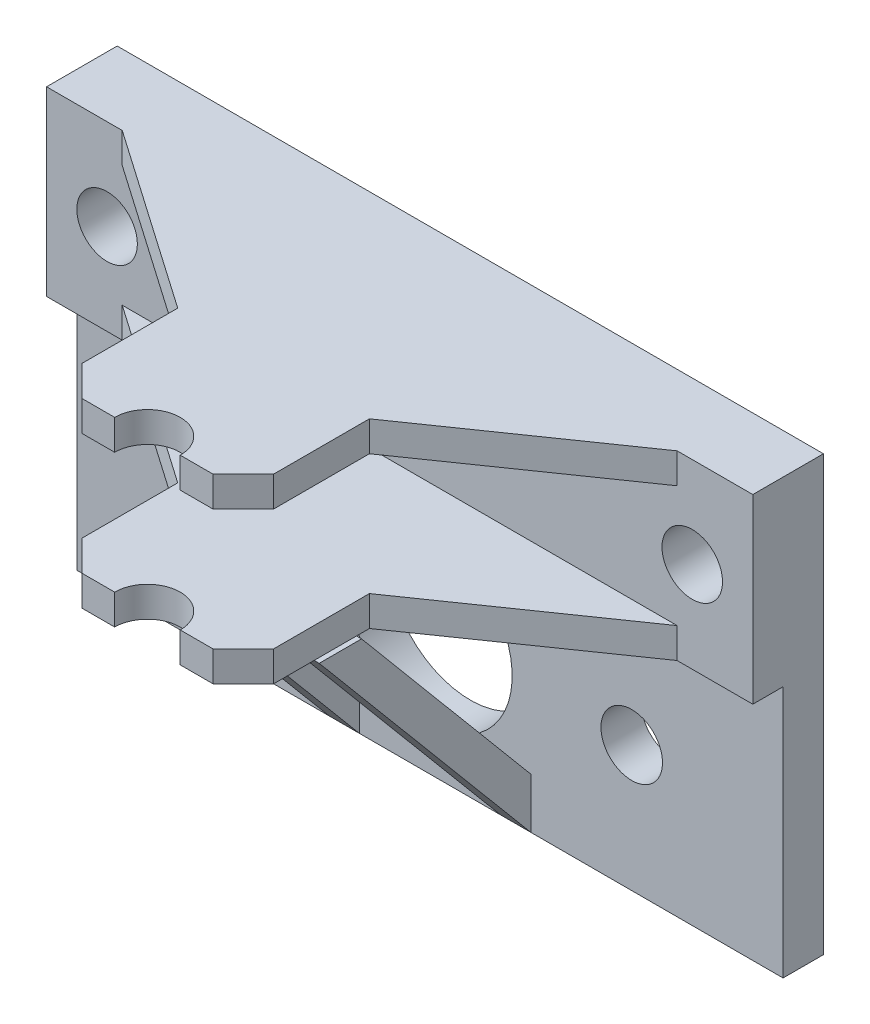
SolidWorks part; units mm, degrees
ref_plane "Front Plane" through (0, 0, 0) normal (0, 0, 1) x (1, 0, 0)
ref_plane "Top Plane" through (0, 0, 0) normal (0, 1, 0) x (1, 0, 0)
ref_plane "Right Plane" through (0, 0, 0) normal (1, 0, 0) x (0, 0, -1)
sketch "Sketch1" plane through (0, 0, 0) normal (0, 1, 0) x (1, 0, 0)
  line L1 (0, 0) -> (55, 0) construction
  line L2 (0, 0) -> (0, 25) construction
  line L3 (0, 25) -> (55, 25) construction
  line L4 (55, 0) -> (55, 25) construction
  line L6 (0, 25) -> (55, 25)
  line L10 (18, 0) -> (24.25, 0)
  line L11 (27.5, 0) -> (27.5, 25) construction
  line L13 (37, 0) -> (30.75, 0)
  line L14 (18, 0) -> (18, 12.5)
  line L15 (18, 12.5) -> (0, 25)
  line L16 (37, 12.5) -> (55, 25)
  line L17 (37, 0) -> (37, 12.5)
  circle A0 centre (27.5, 0) radius 3.25 construction
  arc A1 (24.25, 0) -> (30.75, 0) centre (27.5, 0) cw
  point P14 (27.5, 12.5)
  dimension "D1" = 6.5
  dimension "D2" = 55
  dimension "D3" = 25
  dimension "D4" = 18
extrude "Boss-Extrude1" add sketch "Sketch1" along normal blind 3
sketch "Sketch2" plane through (0, 0, -25) normal (0, 0, -1) x (-1, 0, 0)
  line L0 (-55, 3) -> (0, 3) construction
  line L1 (-62.5, 3) -> (7.5, 3)
  line L2 (-62.5, 3) -> (-62.5, -15)
  line L3 (-62.5, -15) -> (7.5, -15)
  line L4 (7.5, 3) -> (7.5, -15)
  line L5 (-27.5, 3) -> (-27.5, -15) construction
  line L6 (-62.5, -6) -> (-56.5, -6) construction
  circle A0 centre (-56.5, -6) radius 3
  circle A1 centre (1.5, -6) radius 3
  point P6 (-27.5, 3)
  point P7 (-27.5, 3)
  dimension "D3" = 6
  dimension "D1" = 70
  dimension "D2" = 18
  dimension "D4" = 6
extrude "Boss-Extrude2" add sketch "Sketch2" along normal blind 3
ref_plane "Plane1" through (0, -6, 0) normal (0, 1, 0) x (1, 0, 0)
mirror "Mirror1" about plane through (0, -6, 0) normal (0, 1, 0) of "Boss-Extrude1"
chamfer "Chamfer1" distance 3 angle 45 4 edges at (37, 1.5, 0) (18, 1.5, 0) (37, -13.5, 0) (18, -13.5, 0)
sketch "Sketch4" plane through (0, 0, -28) normal (0, 0, -1) x (-1, 0, 0)
  line L0 (7.5, -15) -> (7.5, 3) construction
  line L1 (-62.5, 3) -> (7.5, 3)
  line L2 (-62.5, 3) -> (-62.5, -40)
  line L3 (-62.5, -40) -> (7.5, -40)
  line L4 (7.5, 3) -> (7.5, -40)
  line L5 (7.5, -15) -> (-62.5, -40) construction
  line L6 (-62.5, -15) -> (7.5, -15) construction
  line L7 (-27.5, -27.5) -> (-47.5, -27.5) construction
  line L8 (-27.5, -15) -> (-27.5, 3) construction
  circle A0 centre (-56.5, -6) radius 3
  circle A1 centre (-56.5, -6) radius 3 construction
  circle A2 centre (1.5, -6) radius 3
  circle A3 centre (-27.5, -27.5) radius 8.15
  circle A4 centre (-47.5, -27.5) radius 3.05
  circle A5 centre (-7.5, -27.5) radius 3.05
  dimension "D1" = 16.3
  dimension "D3" = 6.1
  dimension "D2" = 25
  dimension "D4" = 20
extrude "Boss-Extrude3" add sketch "Sketch4" along normal blind 4
ref_plane "Plane2" through (27.5, 0, 0) normal (1, 0, 0) x (0, 0, -1)
ref_plane "Plane3" through (37.5, 0, 0) normal (1, 0, 0) x (0, 0, -1)
sketch "Sketch5" plane through (37.5, 0, 0) normal (1, 0, 0) x (0, 0, -1)
  line L0 (28, -40) -> (7.0225, -15)
  line L1 (7.0225, -15) -> (11.218, -15)
  line L2 (11.218, -15) -> (28, -35)
  line L3 (28, -35) -> (28, -40)
  line L4 (28, -15) -> (28, -40) construction
  line L5 (3, -15) -> (12.5, -15) construction
  line L6 (12.5, -15) -> (25, -15) construction
  dimension "D1" = 40
  dimension "D2" = 5
extrude "Boss-Extrude4" add sketch "Sketch5" against normal blind 3
mirror "Mirror2" about plane through (27.5, 0, 0) normal (1, 0, 0) of "Boss-Extrude4"
